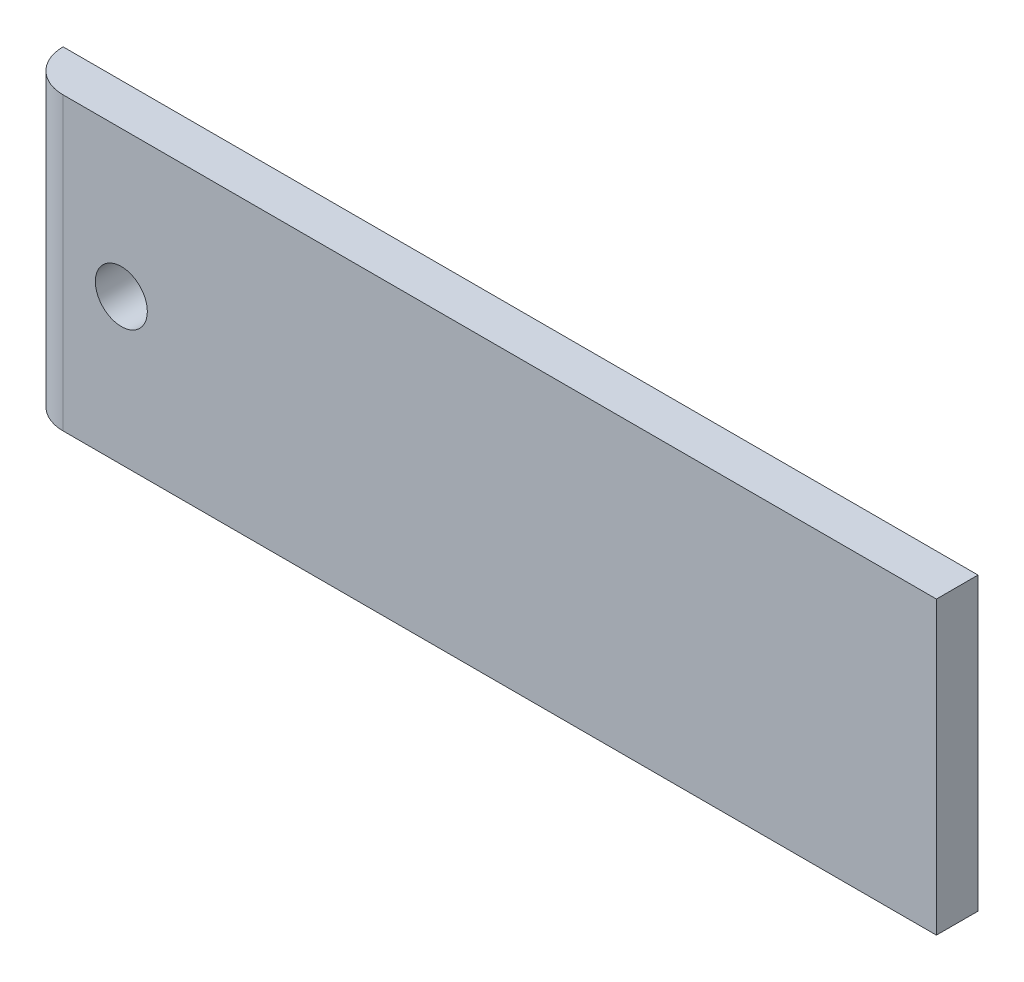
SolidWorks part; units mm, degrees
material "PE High Density"
ref_plane "Front Plane" through (0, 0, 0) normal (0, 0, 1) x (1, 0, 0)
ref_plane "Top Plane" through (0, 0, 0) normal (0, 1, 0) x (1, 0, 0)
ref_plane "Right Plane" through (0, 0, 0) normal (1, 0, 0) x (0, 0, -1)
sketch "Sketch1" plane through (0, 0, 0) normal (0, 1, 0) x (1, 0, 0)
  line L1 (0, 0) -> (139.7, 0)
  line L2 (0, 0) -> (0, 6.35)
  line L3 (0, 6.35) -> (139.7, 6.35)
  line L4 (139.7, 0) -> (139.7, 6.35)
  dimension "D1" = 139.7
  dimension "D2" = 6.35
extrude "Boss-Extrude1" add sketch "Sketch1" along normal blind 44.45
fillet "Fillet1" radius 6.35 1 edges at (0, 22.225, 0)
extrude "Cut-Extrude2" cut sketch "Sketch4" against normal blind 254
sketch "Sketch4" plane through (69.9488, 1.4152, 0) normal (0, 0, 1) x (1, 0, 0)
  circle A0 centre (-54.7088, 20.8098) radius 3.9687
